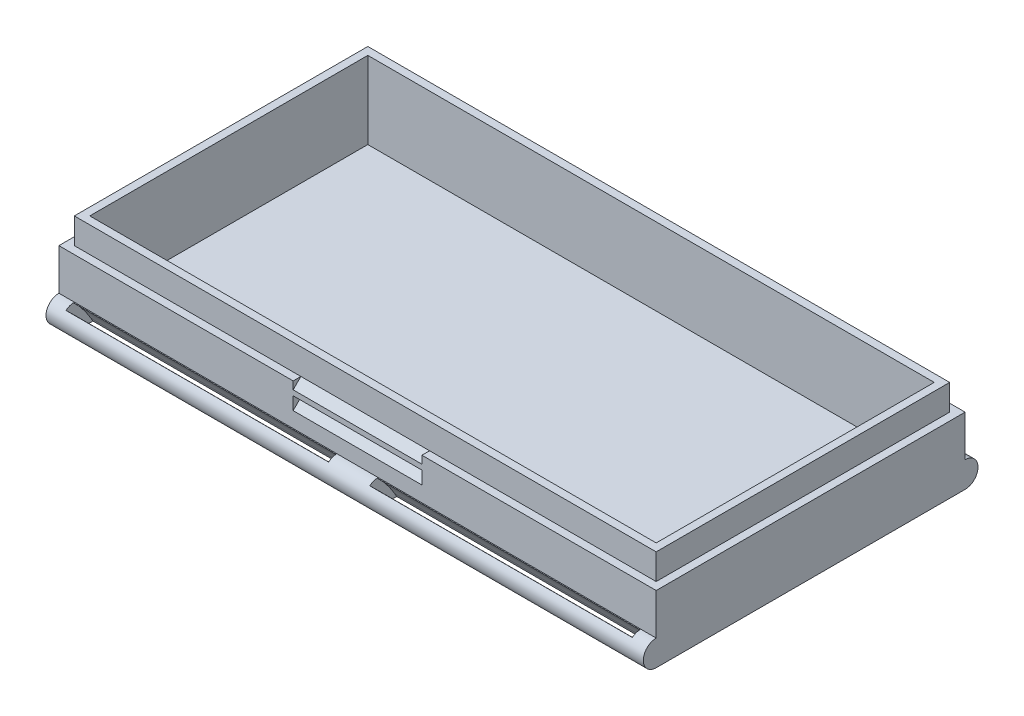
SolidWorks part; units mm, degrees
ref_plane "Front Plane" through (0, 0, 0) normal (0, 0, 1) x (1, 0, 0)
ref_plane "Top Plane" through (0, 0, 0) normal (0, 1, 0) x (1, 0, 0)
ref_plane "Right Plane" through (0, 0, 0) normal (1, 0, 0) x (0, 0, -1)
sketch "Sketch1" plane through (0, 0, 0) normal (0, 1, 0) x (1, 0, 0)
  line L0 (-58, 30) -> (58, 30)
  line L1 (-55, -27) -> (55, -27)
  line L2 (-55, -27) -> (-55, 27)
  line L3 (-55, 27) -> (55, 27)
  line L4 (55, -27) -> (55, 27)
  line L5 (-55, -27) -> (55, 27) construction
  line L6 (-55, 27) -> (55, -27) construction
  line L7 (58, -30) -> (58, 30)
  line L8 (-58, -30) -> (58, -30)
  line L9 (-58, -30) -> (-58, 30)
  point P0 (0, 0)
  point P10 (0, 0)
  dimension "D1" = 110
  dimension "D2" = 54
  dimension "D3" = 3
extrude "Boss-Extrude1" add sketch "Sketch1" along normal blind 10
sketch "Sketch2" plane through (0, 0, 0) normal (0, -1, 0) x (1, 0, 0)
  line L4 (-58, 30) -> (-58, -30)
  line L5 (-58, -30) -> (58, -30)
  line L6 (58, -30) -> (58, 30)
  line L7 (58, 30) -> (-58, 30)
  line L8 (-58, 30) -> (-58, -30)
  line L9 (-58, -30) -> (58, -30)
  line L10 (58, -30) -> (58, 30)
  line L11 (58, 30) -> (-58, 30)
  dimension "D1" = 0
extrude "Boss-Extrude2" add sketch "Sketch2" along normal blind 3
sketch "Sketch3" plane through (0, 0, 0) normal (1, 0, 0) x (0, 0, -1)
  line L0 (-28.5, 10) -> (-31, 10)
  line L1 (-31, 10) -> (-31, 4)
  line L3 (-28.5, 7.5) -> (-30, 7.5)
  line L4 (-30, 7.5) -> (-30, 8.5)
  line L5 (-30, 8.5) -> (-28.5, 10)
  line L6 (-28.5, 7.5) -> (-28.5, 6.5)
  line L7 (-28.5, 6.5) -> (-31, 4)
  line L8 (-30, 10) -> (-30, -3) construction
  line L9 (30, 10) -> (-30, 10) construction
  point P2 (0, 0)
  point P7 (-28.8768, 5.8706)
  point P8 (-33.588, 1.7381)
  point P13 (0, 0)
  dimension "D1" = 1.5
  dimension "D2" = 45
  dimension "D3" = 1
  dimension "D4" = 1
  dimension "D5" = 1
extrude "Cut-Extrude1" cut sketch "Sketch3" against normal mid plane 25
mirror "Mirror1" about plane through (0, 0, 0) normal (0, 0, 1) of "Cut-Extrude1"
sketch "Sketch4" plane through (0, 0, 0) normal (1, 0, 0) x (0, 0, -1)
  line L0 (30, 8.5) -> (30, 10) construction
  line L1 (30, 2) -> (30, -3)
  arc A0 (30, 2) -> (30, -3) centre (30, -0.5) cw
  dimension "D1" = 5
extrude "Boss-Extrude4" add sketch "Sketch4" along normal up to surface and the other way up to surface up to face at (58, 3.5, 0) other way up to face at (-58, 3.5, 0)
sketch "Sketch5" plane through (0, 0, 0) normal (1, 0, 0) x (0, 0, -1)
  line L0 (30, -3) -> (-30, -3) construction
  line L1 (26.7876, -2.3) -> (26.3834, -3)
  line L2 (26.3834, -3) -> (28, -3)
  line L3 (32.5, 2.1264) -> (32.5, 3.8529)
  line L8 (-27, 0) -> (27, 0)
  line L9 (27, 0) -> (27, 10)
  line L10 (27, 10) -> (-27, 10)
  line L11 (-27, 10) -> (-27, 0)
  line L12 (-27, 0) -> (27, 0) construction
  line L13 (27, 0) -> (27, 10) construction
  line L14 (27, 10) -> (-27, 10) construction
  line L15 (-27, 10) -> (-27, 0) construction
  arc A0 (32.5, 2.1264) -> (28, -3) centre (43.104, -11.7203) ccw
  arc A2 (32.5, 3.8529) -> (26.7876, -2.3) centre (43.104, -11.7203) ccw
  arc A3 (33.288, 2.6957) -> (28, -3) centre (43.104, -11.7203) ccw construction
  arc A4 (30, -3) -> (30, 2) centre (30, -0.5) ccw construction
  point P3 (0, 0)
  point P4 (33.0217, -0.2252)
  point P5 (33.0148, 1.2807)
  point P6 (0, 0)
  point P16 (27.2783, -2.2842)
  point P18 (33.3118, 0.8926)
  point P20 (27.2248, -2.0739)
  point P21 (32.8684, 1.5445)
  point P23 (32.6195, -4.8133)
  point P27 (32.5, 3.8529)
  dimension "D3" = 2
  dimension "D4" = 60
  dimension "D1" = 1.4
  dimension "D2" = 0
extrude "Boss-Extrude5" add sketch "Sketch5" along normal mid plane 110 separate body
sketch "Sketch6" plane through (0, 0, 0) normal (1, 0, 0) x (0, 0, -1)
  line L0 (26.3834, -3) -> (28, -3) construction
  line L1 (26.7876, -2.3) -> (26.3834, -3) construction
  line L2 (32.5, 2.1264) -> (32.5, 3.8529) construction
  line L3 (26.3834, -3) -> (28, -3)
  line L4 (26.7876, -2.3) -> (26.3834, -3)
  line L5 (32.5, 2.1264) -> (32.5, 3.8529)
  arc A0 (32.5, 2.1264) -> (28, -3) centre (43.104, -11.7203) ccw construction
  arc A1 (32.5, 3.8529) -> (26.7876, -2.3) centre (43.104, -11.7203) ccw construction
  arc A2 (32.5, 2.1264) -> (28, -3) centre (43.104, -11.7203) ccw
  arc A3 (32.5, 3.8529) -> (26.7876, -2.3) centre (43.104, -11.7203) ccw
extrude "Cut-Extrude2" cut sketch "Sketch6" against normal mid plane 8
mirror "Mirror2" about plane through (0, 0, 0) normal (0, 0, 1) of bodies 108 109
mirror "Mirror3" about plane through (0, 0, 0) normal (0, 0, 1) of "Boss-Extrude4"
combine bodies "Combine2" operation type subtract main body 113 bodies to subtract 108 109 112 111
sketch "Sketch7" plane through (0, 10, 0) normal (0, 1, 0) x (1, 0, 0)
  line L0 (-12.5, 30) -> (-58, 30) construction
  line L1 (56.5, -28.5) -> (-56.5, -28.5)
  line L2 (56.5, -28.5) -> (56.5, 28.5)
  line L3 (56.5, 28.5) -> (-56.5, 28.5)
  line L4 (-56.5, -28.5) -> (-56.5, 28.5)
  line L5 (56.5, -28.5) -> (-56.5, 28.5) construction
  line L6 (56.5, 28.5) -> (-56.5, -28.5) construction
  line L7 (-58, 30) -> (-58, -30) construction
  line L9 (55, -27) -> (-55, -27)
  line L10 (55, -27) -> (55, 27)
  line L11 (55, 27) -> (-55, 27)
  line L12 (-55, -27) -> (-55, 27)
  line L13 (55, -27) -> (-55, 27) construction
  line L14 (55, 27) -> (-55, -27) construction
  point P0 (0, 0)
  point P10 (0, 0)
  dimension "D1" = 1.5
  dimension "D2" = 1.5
extrude "Boss-Extrude6" add sketch "Sketch7" along normal blind 5
